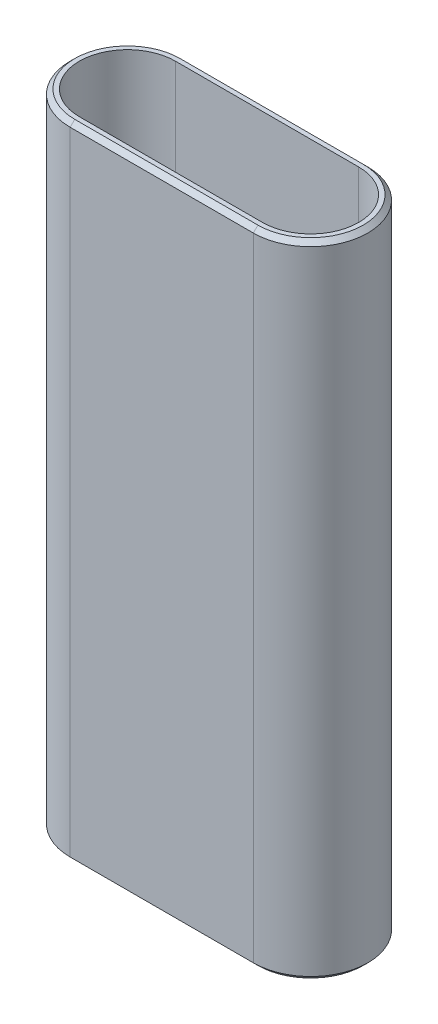
SolidWorks part; units mm, degrees
ref_plane "Front Plane" through (0, 0, 0) normal (0, 0, 1) x (1, 0, 0)
ref_plane "Top Plane" through (0, 0, 0) normal (0, 1, 0) x (1, 0, 0)
ref_plane "Right Plane" through (0, 0, 0) normal (1, 0, 0) x (0, 0, -1)
sketch "Sketch2" plane through (0, 12, 0) normal (0, -1, 0) x (1, 0, 0)
  line L8 (5.45, 3.45) -> (5.45, -3.45) construction
  line L9 (-7.45, -5.65) -> (7.45, -5.65)
  line L10 (-7.45, -5.65) -> (-7.45, 5.65)
  line L11 (-7.45, 5.65) -> (7.45, 5.65)
  line L12 (4.15, -3.65) -> (4.15, 3.65)
  line L13 (4.15, 3.65) -> (-4.15, 3.65)
  line L14 (-4.15, 3.65) -> (-4.15, -3.65)
  line L15 (-4.15, -3.65) -> (4.15, -3.65)
  line L16 (4.15, -3.65) -> (4.15, 3.65)
  line L17 (4.15, 3.65) -> (-4.15, 3.65)
  line L18 (-4.15, 3.65) -> (-4.15, -3.65)
  line L19 (-4.15, -3.65) -> (4.15, -3.65)
  line L20 (7.45, -5.65) -> (7.45, 5.65)
  line L21 (0, 5.65) -> (0, -5.65) construction
  line L22 (-7.45, 0) -> (7.45, 0) construction
  point P0 (0, 0)
  dimension "D2" = 2
  dimension "D3" = 2
  dimension "D4" = 8.3
  dimension "D5" = 7.3
  dimension "D1" = 0.2
extrude "Boss-Extrude1" add sketch "Sketch2" along normal offset from surface (12.6 mm away) 0.6 offset beyond the face yes
sketch "Sketch4" plane through (0, 0, 0) normal (1, 0, 0) x (0, 0, -1)
  line L1 (-1.6, 9.8) -> (-1.6, 8) construction
  line L2 (1.6, 8) -> (1.6, 9.8) construction
  line L3 (2.75, 8) -> (1.6, 8) construction
  line L4 (-1.6, 8) -> (-2.75, 8) construction
  line L5 (-2.75, 8) -> (-2.75, 12) construction
  line L6 (-2.75, 12) -> (-3.45, 12) construction
  line L7 (-3.45, 12) -> (-3.45, 0) construction
  line L8 (-3.45, 0) -> (3.45, 0) construction
  line L9 (3.45, 0) -> (3.45, 12) construction
  line L10 (3.45, 12) -> (2.75, 12) construction
  line L11 (2.75, 12) -> (2.75, 8) construction
  line L13 (-1.6, 9.8) -> (-1.6, 8) construction
  line L14 (1.6, 8) -> (1.6, 9.8) construction
  line L15 (2.75, 8) -> (1.6, 8) construction
  line L16 (-1.6, 8) -> (-2.75, 8) construction
  line L17 (-2.75, 8) -> (-2.75, 12) construction
  line L18 (-2.75, 12) -> (-3.45, 12) construction
  line L19 (-3.45, 12) -> (-3.45, 0) construction
  line L20 (-3.45, 0) -> (3.45, 0) construction
  line L21 (3.45, 0) -> (3.45, 12) construction
  line L22 (3.45, 12) -> (2.75, 12) construction
  line L23 (2.75, 12) -> (2.75, 8) construction
  line L24 (0, -990) -> (0, 49010) construction
  line L25 (-2.3, 10.1) -> (2.3, 10.1)
  line L26 (-2.3, 10.1) -> (-2.3, 7)
  line L27 (-2.3, 7) -> (2.3, 7)
  line L28 (1.6, 10) -> (-1.6, 10)
  line L29 (-1.6, 10) -> (-1.6, 9.8)
  line L30 (-1.6, 9.8) -> (1.6, 9.8)
  line L31 (1.6, 9.8) -> (1.6, 10)
  line L32 (1.6, 10) -> (-1.6, 10) construction
  line L33 (-1.6, 10) -> (-1.6, 9.8) construction
  line L34 (2.3, 10.1) -> (2.3, 7)
  line L35 (1.6, 9.8) -> (1.6, 10) construction
  point P20 (0, 10)
  dimension "D2" = 0.7
  dimension "D3" = 0.1
  dimension "D4" = 1
  dimension "D1" = 0
extrude "Cut-Extrude1" cut sketch "Sketch4" against normal through all both and the other way through all
sketch "Sketch5" plane through (0, -0.6, 0) normal (0, -1, 0) x (1, 0, 0)
  line L0 (-20, 0) -> (20, 0) construction
  line L1 (-20, 12.5) -> (20, 12.5)
  line L2 (-20, -12.5) -> (20, -12.5)
  arc A0 (-20, 12.5) -> (-20, -12.5) centre (-20, 0) ccw
  arc A1 (20, -12.5) -> (20, 12.5) centre (20, 0) ccw
  point P2 (0, 0)
  dimension "D1" = 25
  dimension "D2" = 40
extrude "Boss-Extrude2" add sketch "Sketch5" along normal blind 3
sketch "Sketch7" plane through (0, -0.6, 0) normal (0, 1, 0) x (1, 0, 0)
  line L0 (-20, -10.5) -> (20, -10.5)
  line L1 (20, 10.5) -> (-20, 10.5)
  line L2 (-20, -12.5) -> (20, -12.5)
  line L3 (20, 12.5) -> (-20, 12.5)
  line L4 (-20, -12.5) -> (20, -12.5)
  line L5 (20, 12.5) -> (-20, 12.5)
  arc A0 (20, -10.5) -> (20, 10.5) centre (20, 0) ccw
  arc A1 (-20, 10.5) -> (-20, -10.5) centre (-20, 0) ccw
  arc A2 (-20, 12.5) -> (-20, -12.5) centre (-20, 0) ccw
  arc A3 (20, -12.5) -> (20, 12.5) centre (20, 0) ccw
  arc A4 (-20, 12.5) -> (-20, -12.5) centre (-20, 0) ccw
  arc A5 (20, -12.5) -> (20, 12.5) centre (20, 0) ccw
  dimension "D1" = 0
  dimension "D2" = 2
extrude "Boss-Extrude3" add sketch "Sketch7" along normal blind 137
chamfer "Chamfer1" distance 1 angle 45 8 edges at (32.5, -3.6, 0) (0, -3.6, 12.5) (0, -3.6, -12.5) (-32.5, -3.6, 0) (32.5, 136.4, 0) (0, 136.4, -12.5) (0, 136.4, 12.5) (-32.5, 136.4, 0)
chamfer "Chamfer2" distance 0.8 angle 45 8 edges at (-7.45, 12, 0) (0, 12, -5.65) (7.45, 12, 0) (0, 12, 5.65) (0, 12, 3.65) (4.15, 12, 0) (0, 12, -3.65) (-4.15, 12, 0)
chamfer "Chamfer3" distance 2 angle 45 4 edges at (-7.45, 5.3, 5.65) (-7.45, 5.3, -5.65) (7.45, 5.3, -5.65) (7.45, 5.3, 5.65)
equation "\"case_length\"= 140"
equation "\"plate_thickness\"= 3"
equation "\"D1@Boss-Extrude2\"=\"plate_thickness\""
equation "\"D1@Boss-Extrude3\"=\"case_length\"-\"plate_thickness\""
equation "\"case_height\"= 25"
equation "\"case_width\"= 65"
equation "\"case_to_shell_offset\"= 19.6"
equation "\"body_tip_distance\"= 30"
equation "\"D2@Sketch5\"=\"case_width\"-\"case_height\""
equation "\"D1@Sketch5\"=\"case_height\""
